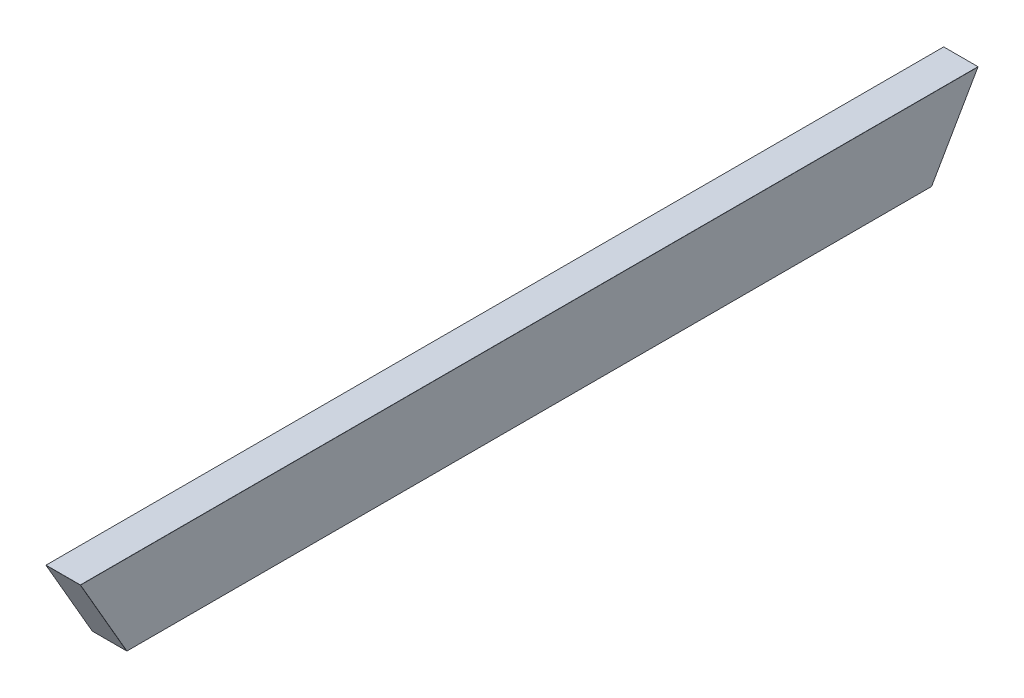
SolidWorks part; units mm, degrees
ref_plane "Front Plane" through (0, 0, 0) normal (0, 0, 1) x (1, 0, 0)
ref_plane "Top Plane" through (0, 0, 0) normal (0, 1, 0) x (1, 0, 0)
ref_plane "Right Plane" through (0, 0, 0) normal (1, 0, 0) x (0, 0, -1)
sketch "Sketch1" plane through (0, 0, 0) normal (0, 0, 1) x (1, 0, 0)
  line L1 (1.5, 3.5) -> (-1.5, 3.5)
  line L2 (1.5, 3.5) -> (1.5, -3.5)
  line L3 (1.5, -3.5) -> (-1.5, -3.5)
  line L4 (-1.5, 3.5) -> (-1.5, -3.5)
  line L5 (1.5, 3.5) -> (-1.5, -3.5) construction
  line L6 (1.5, -3.5) -> (-1.5, 3.5) construction
  point P0 (0, 0)
  dimension "D1" = 7
  dimension "D2" = 3
extrude "Boss-Extrude1" add sketch "Sketch1" along normal mid plane 78
draft "Draft1" type of draft neutral plane draft angle 30 faces to draft 1 face at (0, 0, 39) neutral plane through (1.5, 3.5, 39) neutral plane normal (0, 1, 0) reverse direction yes parameters "D1"=30
draft "Draft2" type of draft neutral plane draft angle 30 faces to draft 1 face at (0, 0, -39) neutral plane through (1.5, 3.5, 39) neutral plane normal (0, 1, 0) reverse direction yes parameters "D1"=30
chamfer "Chamfer1" distance 0.01 angle 45 4 edges at (-1.5, 3.5, 0) (-1.5, -3.5, 0) (1.5, 3.5, 0) (1.5, -3.5, 0)
chamfer "Chamfer2" distance 0.01 angle 45 14 edges at (1.495, 3.495, 38.9971) (1.5, 0, 36.9793) (0, -3.5, 34.9585) (-1.5, 0, 36.9793) (-1.495, 3.495, 38.9971) (0, 3.5, 39) (-1.495, -3.495, -34.9614) (0, -3.5, -34.9585) (1.495, -3.495, -34.9614) (1.5, 0, -36.9793) (1.495, 3.495, -38.9971) (0, 3.5, -39) (-1.495, 3.495, -38.9971) (-1.5, 0, -36.9793)
